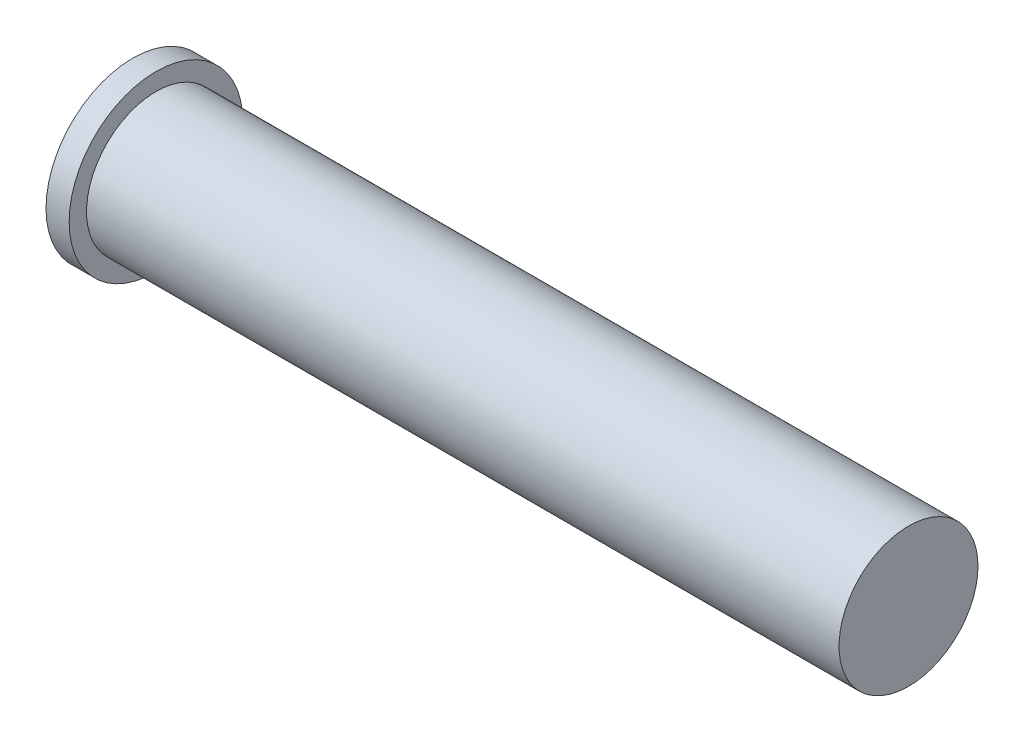
SolidWorks part; units mm, degrees
ref_plane "Front Plane" through (0, 0, 0) normal (0, 0, 1) x (1, 0, 0)
ref_plane "Top Plane" through (0, 0, 0) normal (0, 1, 0) x (1, 0, 0)
ref_plane "Right Plane" through (0, 0, 0) normal (1, 0, 0) x (0, 0, -1)
sketch "Sketch1" plane through (0, 0, 0) normal (1, 0, 0) x (0, 0, -1)
  circle A0 centre (0, 0) radius 6
  circle A1 centre (0, 0) radius 7.5
  dimension "D1" = 12
  dimension "D2" = 15
extrude "Boss-Extrude2" add sketch "Sketch1" along normal blind 2 contours A1 A0 region at (0, 0, 7.2879)
extrude "Boss-Extrude3" add sketch "Sketch1<4>" along normal blind 67 contours A0 region at (0, 0, 0)
sketch "Sketch1<4>" plane through (0, 0, 0) normal (1, 0, 0) x (0, 0, -1) same geometry as "Sketch1"
